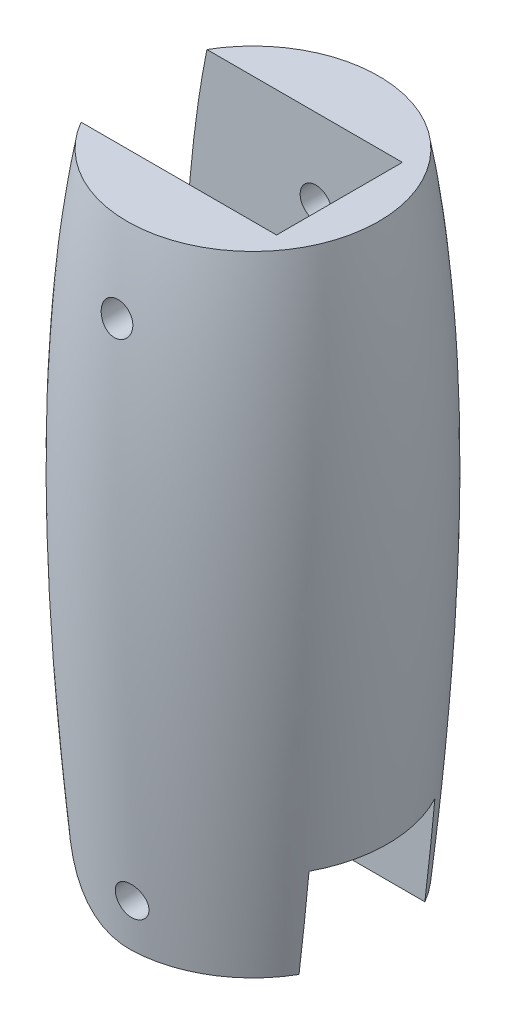
SolidWorks part; units mm, degrees
ref_plane "Front Plane" through (0, 0, 0) normal (0, 0, 1) x (1, 0, 0)
ref_plane "Top Plane" through (0, 0, 0) normal (0, 1, 0) x (1, 0, 0)
ref_plane "Right Plane" through (0, 0, 0) normal (1, 0, 0) x (0, 0, -1)
sketch "Sketch1" plane through (0, 0, 0) normal (1, 0, 0) x (0, 0, -1)
  line L0 (0, 20) -> (0, -20)
  line L1 (0, 20) -> (8, 20)
  line L2 (0, -20) -> (8, -20)
  line L3 (13.2094, -9.5442) -> (2.7906, 49.5442) construction
  spline S0 degree 2 poles (8, 20) (10.6047, 5.2279) (8, -20) knots 0 0 0 1 1 1
  point P3 (0, 0)
  dimension "D3" = 100
  dimension "D4" = 30
  dimension "D1" = 40
  dimension "D2" = 8
revolve "Revolve1" add sketch "Sketch1" angle 360 about L0
sketch "Sketch2" plane through (0, 0, 0) normal (1, 0, 0) x (0, 0, -1)
  line L0 (8, 20) -> (-8, 20) construction
  line L1 (-4, 7) -> (4, 7)
  line L2 (-4, 7) -> (-4, 20)
  line L3 (-4, 20) -> (4, 20)
  line L4 (4, 7) -> (4, 20)
  line L5 (-8, -20) -> (8, -20) construction
  line L6 (-4, -20) -> (4, -20)
  line L7 (-4, -20) -> (-4, -8)
  line L8 (-4, -8) -> (4, -8)
  line L9 (4, -20) -> (4, -8)
  point P12 (0, -8)
  point P14 (0, 7)
  dimension "D1" = 8
  dimension "D2" = 12
  dimension "D3" = 13
extrude "Cut-Extrude1" cut sketch "Sketch2" along normal blind 5.5 and the other way through all
sketch "Sketch3" plane through (0, 0, 0) normal (0, 0, 1) x (1, 0, 0)
  line L0 (0.5359, -20) -> (0.5359, -17) construction
  line L1 (-6.9282, -20) -> (8, -20) construction
  line L2 (0, 20) -> (0, 15) construction
  line L4 (8, 20) -> (-6.9282, 20) construction
  circle A0 centre (0, 15) radius 1
  circle A1 centre (0.5359, -17) radius 1
  dimension "D3" = 2
  dimension "D1" = 3
  dimension "D2" = 5
extrude "Cut-Extrude2" cut sketch "Sketch3" against normal through all and the other way through all
sketch "Sketch5" plane through (0, 0, 0) normal (0, 0, 1) x (1, 0, 0)
  line L2 (-6.9282, -20) -> (8, -20) construction
  line L3 (-6.9282, -20) -> (8, -20)
  line L4 (-6.9282, 20) -> (5.5, 20) construction
  line L5 (-6.9282, 20) -> (5.5, 20)
  arc A0 (-7.6463, 15.6441) -> (-2.6879, 20) centre (-2.6879, 15) cw
  arc A2 (-7.6838, -12.6928) -> (0.2861, -20) centre (0.2861, -12) ccw
  spline S0 degree 3 poles (1989.7334, 13.6804) (95.194, 145.6186) (-0.6581, 84.3334) (-18.3549, -88.9086) (160.5472, -211.6882) (-1997.4798, -83.424) knots -15.830473 -15.830473 -15.830473 -15.830473 0.5 0.5 24.126069 24.126069 24.126069 24.126069 only from (-6.9282, 20) to (-8.3247, 7) construction
  spline S1 degree 3 poles (1867.3193, 638.8469) (-2007.9878, -77.1233) (1999.3884, -63.5148) (-1821.4076, -774.4397) knots -39.104503 -39.104503 -39.104503 -39.104503 49.459978 49.459978 49.459978 49.459978 only from (-8.0389, -8) to (-6.9282, -20) construction
  spline S3 degree 3 poles (-8.0389, -8) (-7.7817, -12.0105) (-7.4039, -16.0098) (-6.9282, -20) knots 0 0 0 0 1 1 1 1
  spline S4 degree 3 poles (1867.3193, 638.8469) (-2007.9878, -77.1233) (1999.3884, -63.5148) (-1821.4076, -774.4397) knots -39.104503 -39.104503 -39.104503 -39.104503 49.459978 49.459978 49.459978 49.459978 only from (-8.0389, -8) to (-6.9282, -20) construction
  spline S5 degree 3 poles (-8.0389, -8) (-7.7817, -12.0105) (-7.4039, -16.0098) (-6.9282, -20) knots 0 0 0 0 1 1 1 1
  spline S6 degree 3 poles (-6.9282, 20) (-7.3649, 17.8552) (-7.6694, 15.6963) (-8.1123, 11.3605) (-8.249, 9.1835) (-8.3247, 7) knots 0 0 0 0 0.5 0.5 1 1 1 1
  dimension "D1" = 5
  dimension "D2" = 8
extrude "Cut-Extrude4" cut sketch "Sketch5" against normal blind 20 from offset 10 contours S3 | A2 S5 L3 region at (-5.5269, -18.394, 0)
sketch "Sketch6" plane through (0, 7, 0) normal (0, 1, 0) x (1, 0, 0)
  circle A0 centre (-3, 0) radius 0.5
  circle A1 centre (4, 0) radius 0.5
  dimension "D1" = 1
  dimension "D2" = 1
  dimension "D3" = 3
  dimension "D4" = 4
extrude "Cut-Extrude5" cut sketch "Sketch6" against normal through all
sketch "Sketch7" plane through (5.5, 0, 0) normal (-1, 0, 0) x (0, 0, 1)
  line L0 (4, -8) -> (4, -20) construction
  line L1 (-4, -20) -> (4, -20)
  line L2 (-4, -20) -> (-4, -14)
  line L3 (-4, -14) -> (4, -14)
  line L4 (4, -20) -> (4, -14)
  dimension "D1" = 6
extrude "Cut-Extrude6" cut sketch "Sketch7" against normal through all
